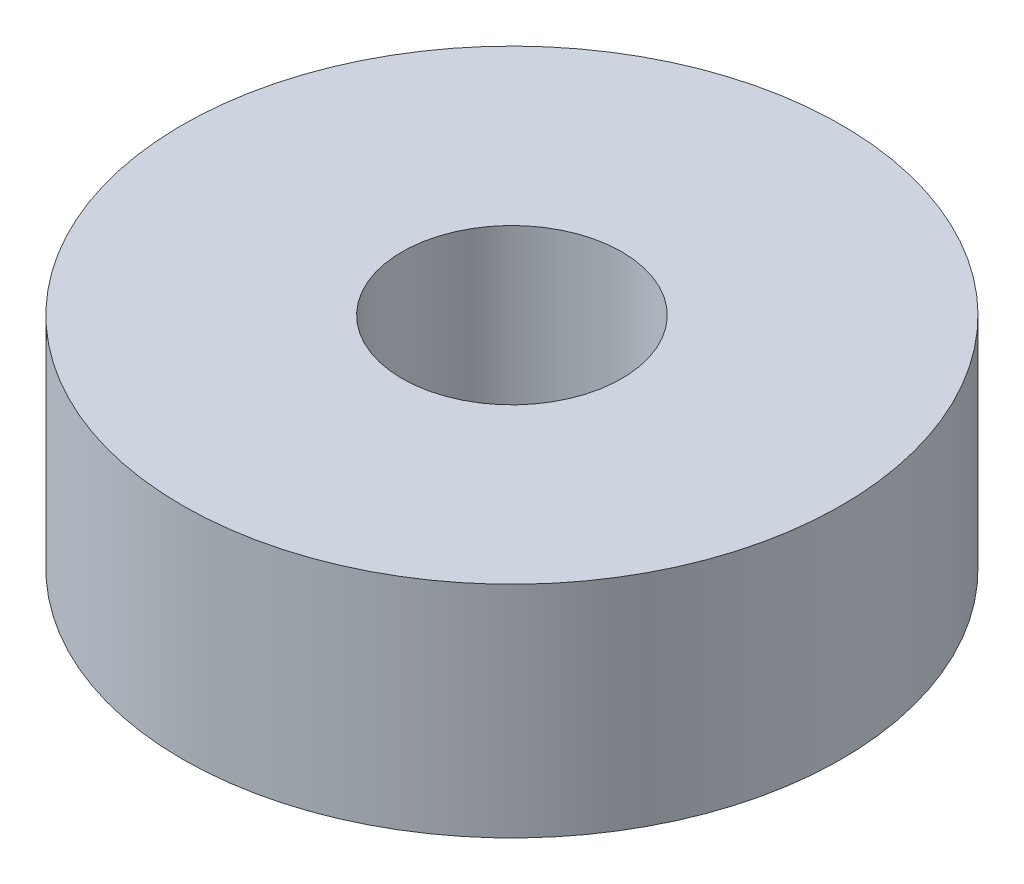
SolidWorks part; units mm, degrees
ref_plane "Front" through (0, 0, 0) normal (0, 0, 1) x (1, 0, 0)
ref_plane "Top" through (0, 0, 0) normal (0, 1, 0) x (1, 0, 0)
ref_plane "Right" through (0, 0, 0) normal (1, 0, 0) x (0, 0, -1)
sketch "Sketch1" plane through (0, 0, 0) normal (0, 1, 0) x (1, 0, 0)
  circle A0 centre (0, 0) radius 1.5875
  circle A1 centre (0, 0) radius 4.7625
  dimension "D1" = 3.175
  dimension "D2" = 3.175
extrude "Boss-Extrude1" add sketch "Sketch1" along normal blind 3.175
